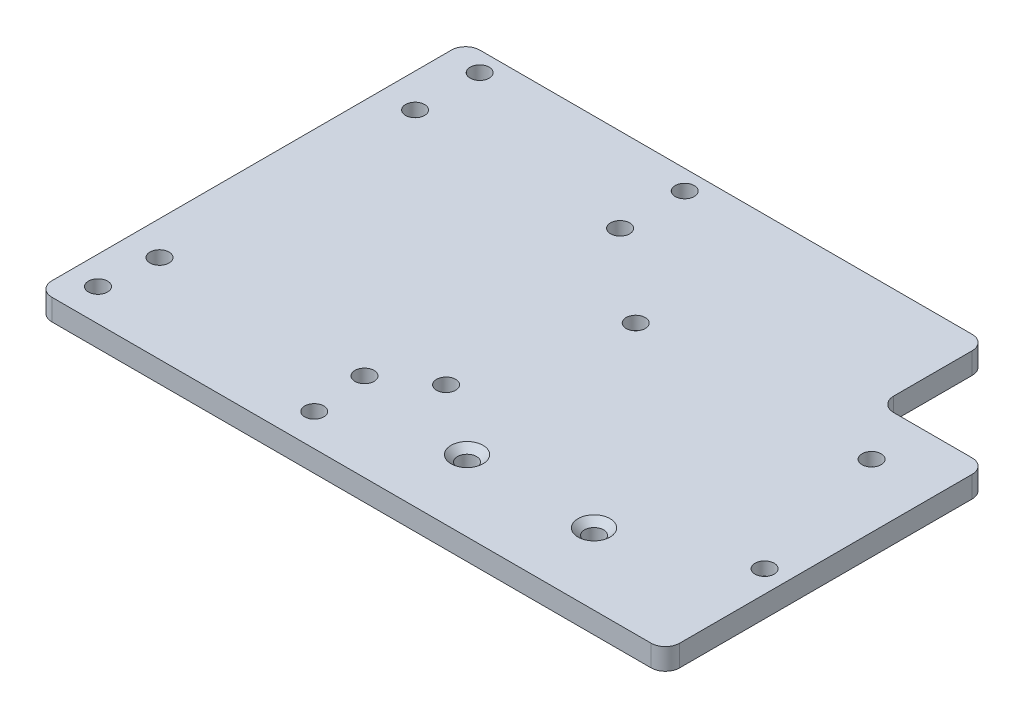
SolidWorks part; units mm, degrees
note: '?' marks a value the reader was unsure of.
ref_plane "Front Plane" through (0, 0, 0) normal (0, 0, 1) x (1, 0, 0)
ref_plane "Top Plane" through (0, 0, 0) normal (0, 1, 0) x (1, 0, 0)
ref_plane "Right Plane" through (0, 0, 0) normal (1, 0, 0) x (0, 0, -1)
sketch "Sketch1" plane through (0, 0, 0) normal (0, 1, 0) x (1, 0, 0)
  line L1 (-55.88, -38.1) -> (55.88, -38.1)
  line L2 (-55.88, -38.1) -> (-55.88, 38.1)
  line L3 (-55.88, 38.1) -> (55.88, 38.1)
  line L4 (55.88, -38.1) -> (55.88, 38.1)
  line L5 (-55.88, -38.1) -> (55.88, 38.1) construction
  line L6 (-55.88, 38.1) -> (55.88, -38.1) construction
  point P0 (0, 0)
  dimension "D1" = 111.76
  dimension "D2" = 76.2
extrude "Boss-Extrude1" add sketch "Sketch1" along normal mid plane 3.81
fillet "Fillet1" radius 2.54 4 edges at (55.88, 0, 38.1) (55.88, 0, -38.1) (-55.88, 0, -38.1) (-55.88, 0, 38.1)
hole_wizard "CSK for M3 Flat Head Machine Screw3" [suppressed] positions "Sketch2" profile "Sketch3" countersink size "M3" standard "ANSI Metric"
sketch "Sketch2" plane through (0, 1.5875, 0) normal (0, 1, 0) x (1, 0, 0)
  line L0 (-50, 24.9999) -> (50, 24.9999) construction
  line L1 (50, 24.9999) -> (50, -24.9999) construction
  line L2 (50, -24.9999) -> (-50, -24.9999) construction
  line L3 (-50, -24.9999) -> (-50, 24.9999) construction
  line L6 (0, -1.7463) -> (0, 1.7463) construction
  line L7 (-1.7463, 0) -> (1.7463, 0) construction
  point P0 (-50, 24.9999)
  point P2 (50, 24.9999)
  point P4 (50, -24.9999)
  point P6 (-50, -24.9999)
  point P20 (0, 24.9999)
  point P23 (-50, 0)
  dimension "D1" = 100
  dimension "D2" = 49.9999
sketch "Sketch3" plane through (-50, 1.5875, -24.9999) normal (1, 0, 0) x (0, 0, 1)
  line L0 (0, 0) -> (0, 3.175)
  line L1 (0, 3.175) -> (1.8, 3.175)
  line L2 (1.8, 3.175) -> (1.8, 1.35)
  line L3 (1.8, 1.35) -> (3.15, 0)
  line L5 (3.15, 0) -> (0, 0)
  line L6 (-1.8, 1.35) -> (-3.15, 0) construction
  line L11 (0, -6.35) -> (0, 107.95) construction
  dimension "Thru Hole Dia." = 3.6
  dimension "Thru Hole Depth" = 3.175
  dimension "Near C'Sink Dia." = 6.3
  dimension "Near C'Sink Angle" = 90
hole_wizard "Ø3.8 (3.8) Diameter Hole1" [suppressed] positions "Sketch4" profile "Sketch5" hole size "Ø3.8" standard "ANSI Metric"
sketch "Sketch4" plane through (0, 1.5875, 0) normal (0, 1, 0) x (1, 0, 0)
  line L0 (-1.7463, 0) -> (1.7463, 0) construction
  line L1 (-62.25, 0) -> (62.25, 0) construction
  point P0 (-62.25, 0)
  point P2 (62.25, 0)
  point P11 (0, 0)
  dimension "D1" = 124.5
sketch "Sketch5" plane through (-62.25, 1.5875, 0) normal (1, 0, 0) x (0, 0, 1)
  line L0 (0, 0) -> (0, 3.175)
  line L1 (0, 3.175) -> (1.9, 3.175)
  line L2 (1.9, 3.175) -> (1.9, 0)
  line L5 (1.9, 0) -> (0, 0)
  line L11 (0, -6.35) -> (0, 107.95) construction
  dimension "Thru Hole Dia." = 3.8
  dimension "Thru Hole Depth" = 3.175
hole_wizard "M3 Clearance Hole4" positions "Sketch6" profile "Sketch7" hole size "M3" standard "ANSI Metric" end condition through all
sketch "Sketch6" plane through (0, -1.905, 0) normal (0, -1, 0) x (-1, 0, 0)
  line L0 (13.38, 34.6) -> (49.88, 34.6) construction
  line L2 (50.88, -32.35) -> (12.38, -32.35) construction
  line L11 (53.34, -38.1) -> (-53.34, -38.1) construction
  line L13 (31.63, 34.6) -> (31.63, -32.35) construction
  line L14 (55.88, 35.56) -> (55.88, -35.56) construction
  line L15 (-53.34, 38.1) -> (53.34, 38.1) construction
  point P0 (13.38, 34.6)
  point P2 (49.88, 34.6)
  point P4 (50.88, -32.35)
  point P6 (12.38, -32.35)
  dimension "D1" = 36.5
  dimension "D2" = 5.75
  dimension "D3" = 38.5
  dimension "D4" = 3.5
  dimension "D5" = 24.25
sketch "Sketch7" plane through (-13.38, -1.905, -34.6) normal (1, 0, 0) x (0, 0, -1)
  line L0 (0, 0) -> (0, 3.81)
  line L1 (0, 3.81) -> (1.7, 3.81)
  line L2 (1.7, 3.81) -> (1.7, 0)
  line L5 (1.7, 0) -> (0, 0)
  line L11 (0, -6.35) -> (0, 107.95) construction
  dimension "Thru Hole Dia." = 3.4
  dimension "Thru Hole Depth" = 3.81
hole_wizard "CSK for M3 Flat Head Machine Screw1" positions "Sketch8" profile "Sketch9" countersink size "M3" standard "ANSI Metric" end condition up to next
sketch "Sketch8" plane through (0, -1.905, 0) normal (0, -1, 0) x (-1, 0, 0)
  line L0 (-51.9557, -16.51) -> (4.7447, -16.51) construction
  line L2 (-55.88, -35.56) -> (-55.88, 35.56) construction
  line L3 (53.34, -38.1) -> (-53.34, -38.1) construction
  line L4 (-2.6053, 9.89) -> (-44.6057, 9.89) construction
  line L7 (-23.6055, 9.89) -> (-23.6055, -16.51) construction
  point P0 (-51.9557, -16.51)
  point P2 (4.7447, -16.51)
  point P13 (-44.6057, 9.89)
  point P15 (-2.6053, 9.89)
  dimension "D1" = 56.7004
  dimension "D2" = 3.9243
  dimension "D3" = 21.59
  dimension "D4" = 7.35
  dimension "D5" = 26.4
sketch "Sketch9" plane through (51.9557, -1.905, 16.51) normal (1, 0, 0) x (0, 0, -1)
  line L0 (0, 0) -> (0, 3.81)
  line L1 (0, 3.81) -> (1.7, 3.81)
  line L2 (1.7, 3.81) -> (1.7, 1.45)
  line L3 (1.7, 1.45) -> (3.15, 0)
  line L5 (3.15, 0) -> (0, 0)
  line L6 (-1.7, 1.45) -> (-3.15, 0) construction
  line L11 (0, -6.35) -> (0, 107.95) construction
  dimension "Thru Hole Dia." = 3.4
  dimension "Thru Hole Depth" = 3.81
  dimension "Near C'Sink Dia." = 6.3
  dimension "Near C'Sink Angle" = 90
hole_wizard "CSK for M3 Flat Head Machine Screw2" positions "Sketch10" profile "Sketch11" countersink size "M3" standard "ANSI Metric" end condition up to next
sketch "Sketch10" plane through (0, -1.905, 0) normal (0, -1, 0) x (-1, 0, 0)
  line L0 (49.88, 23.1) -> (49.88, -22.4) construction
  line L4 (49.88, 23.1) -> (13.38, 23.1) construction
  line L5 (13.38, 23.1) -> (13.38, -22.4) construction
  line L6 (13.38, -22.4) -> (49.88, -22.4) construction
  line L8 (49.88, 23.1) -> (49.88, 34.6) construction
  circle A0 centre (49.88, 34.6) radius 1.7 construction
  point P0 (49.88, 23.1)
  point P2 (49.88, -22.4)
  point P17 (13.38, 23.1)
  point P19 (13.38, -22.4)
  dimension "D2" = 57
  dimension "D1" = 45.5
  dimension "D3" = 36.5
sketch "Sketch11" plane through (-49.88, -1.905, -23.1) normal (1, 0, 0) x (0, 0, -1)
  line L0 (0, 0) -> (0, 3.81)
  line L1 (0, 3.81) -> (1.7, 3.81)
  line L2 (1.7, 3.81) -> (1.7, 1.45)
  line L3 (1.7, 1.45) -> (3.15, 0)
  line L5 (3.15, 0) -> (0, 0)
  line L6 (-1.7, 1.45) -> (-3.15, 0) construction
  line L11 (0, -6.35) -> (0, 107.95) construction
  dimension "Thru Hole Dia." = 3.4
  dimension "Thru Hole Depth" = 3.81
  dimension "Near C'Sink Dia." = 6.3
  dimension "Near C'Sink Angle" = 90
sketch "Sketch23" plane through (0, -1.905, 0) normal (0, -1, 0) x (1, 0, 0)
  circle A0 centre (-13.38, 22.4) radius 3.15 construction
  circle A1 centre (-49.88, 22.4) radius 3.15 construction
  circle A2 centre (-13.38, 22.4) radius 3.15
  circle A3 centre (-49.88, 22.4) radius 3.15
  circle A4 centre (-13.38, 22.4) radius 1.7 construction
  circle A5 centre (-49.88, 22.4) radius 1.7 construction
  circle A6 centre (-13.38, 22.4) radius 1.7
  circle A7 centre (-49.88, 22.4) radius 1.7
extrude "Boss-Extrude2" add sketch "Sketch23" against normal up to surface (3.81 mm away) up to face at (-49.88, 1.905, -24.8)
sketch "Sketch12" plane through (0, -1.905, 0) normal (0, -1, 0) x (1, 0, 0)
  line L1 (65.1855, -44.4378) -> (36.83, -44.4378)
  line L2 (65.1855, -44.4378) -> (65.1855, -19.05)
  line L3 (65.1855, -19.05) -> (36.83, -19.05)
  line L4 (36.83, -44.4378) -> (36.83, -19.05)
  line L5 (55.88, 35.56) -> (55.88, -35.56) construction
  line L7 (53.34, -38.1) -> (-53.34, -38.1) construction
  dimension "D1" = 19.05
  dimension "D2" = 19.05
extrude "Cut-Extrude1" cut sketch "Sketch12" against normal through all
hole_wizard "M3 Clearance Hole1" positions "Sketch15" profile "Sketch16" hole size "M3" standard "ANSI Metric" end condition up to next
sketch "Sketch15" plane through (0, -1.905, 0) normal (0, -1, 0) x (-1, 0, 0)
  line L0 (-30.48, -25.4) -> (-7.874, -25.4) construction
  line L2 (53.34, -38.1) -> (-53.34, -38.1) construction
  line L3 (-55.88, -35.56) -> (-55.88, 19.05) construction
  point P0 (-30.48, -25.4)
  point P2 (-7.874, -25.4)
  dimension "D1" = 22.606
  dimension "D2" = 12.7
  dimension "D3" = 25.4
sketch "Sketch16" plane through (30.48, -1.905, 25.4) normal (1, 0, 0) x (0, 0, -1)
  line L0 (0, 0) -> (0, 3.81)
  line L1 (0, 3.81) -> (2.85, 3.81)
  line L2 (1.7, 2.66) -> (1.7, 0)
  line L5 (1.7, 0) -> (0, 0)
  line L7 (2.85, 3.81) -> (1.7, 2.66)
  line L8 (-2.85, 3.81) -> (-1.7, 2.66) construction
  line L11 (0, -6.35) -> (0, 107.95) construction
  dimension "Thru Hole Dia." = 3.4
  dimension "Thru Hole Depth" = 3.81
  dimension "Far C'Sink Dia." = 5.7
  dimension "Far C'Sink Angle" = 90
fillet "Fillet2" radius 2.54 3 edges at (55.88, 0, -19.05) (36.83, 0, -19.05) (36.83, 0, -38.1)
ref_axis "Axis1" [suppressed] through (-50, -1.5875, 24.9999) along (0, 1, 0)?
ref_axis "Axis2" [suppressed] through (50, -1.5875, 24.9999) along (0, 1, 0)?
sketch "Sketch17" [suppressed] plane through (0, 1.905, 0) normal (0, 1, 0) x (1, 0, 0)
  line L0 (-9.88, 0) -> (-55.88, 0) construction
  line L1 (-9.88, 50.8) -> (79.6695, 50.8)
  line L2 (-9.88, 50.8) -> (-9.88, -50.8)
  line L3 (-9.88, -50.8) -> (79.6695, -50.8)
  line L4 (79.6695, 50.8) -> (79.6695, -50.8)
  line L5 (-55.88, 34.925) -> (-55.88, -34.925) construction
  dimension "D1" = 101.6
  dimension "D2" = 46
extrude "Cut-Extrude2" [suppressed] cut sketch "Sketch17" against normal through all both and the other way through all
sketch "Sketch18" [suppressed] plane through (0, 1.905, 0) normal (0, 1, 0) x (1, 0, 0)
  line L0 (-52.705, -38.1) -> (-9.88, -38.1) construction
  line L1 (-37.43, -25.4) -> (-18.38, -25.4)
  line L2 (-37.43, -25.4) -> (-37.43, -44.45)
  line L3 (-37.43, -44.45) -> (-18.38, -44.45)
  line L4 (-18.38, -25.4) -> (-18.38, -44.45)
  line L6 (-9.88, -38.1) -> (-9.88, 38.1) construction
  circle A0 centre (-14.63, -32.35) radius 3.6 construction
  dimension "D5" = 7.2
  dimension "D1" = 19.05
  dimension "D2" = 8.5
  dimension "D3" = 19.05
  dimension "D4" = 12.7
extrude "Cut-Extrude3" [suppressed] cut sketch "Sketch18" against normal through all
fillet "Fillet3" [suppressed] radius 3.175
hole_wizard "M3 Clearance Hole3" [suppressed] positions "Sketch19" profile "Sketch20" hole size "M3" standard "ANSI Metric"
sketch "Sketch19" plane through (0, 1.905, 0) normal (0, 1, 0) x (1, 0, 0)
  line L0 (-52.13, 34.6) -> (-52.13, 7.1) construction
  line L1 (-52.13, 7.1) -> (-13.63, 7.1) construction
  point P0 (-52.13, 7.1)
  point P2 (-13.63, 7.1)
  dimension "D1" = 27.5
  dimension "D2" = 38.5
sketch "Sketch20" plane through (-52.13, 1.905, -7.1) normal (1, 0, 0) x (0, 0, 1)
  line L0 (0, 0) -> (0, 3.81)
  line L1 (0, 3.81) -> (1.8, 3.81)
  line L2 (1.8, 3.81) -> (1.8, 0)
  line L5 (1.8, 0) -> (0, 0)
  line L11 (0, -6.35) -> (0, 107.95) construction
  dimension "Thru Hole Dia." = 3.6
  dimension "Thru Hole Depth" = 3.81
sketch "Sketch21" [suppressed] plane through (0, -1.905, 0) normal (0, -1, 0) x (1, 0, 0)
  line L0 (-51.13, 32.35) -> (-14.63, 32.35) construction
  line L1 (-13.055, -38.1) -> (-52.705, -38.1) construction
  point P4 (-32.88, 32.35)
  point P7 (-32.88, -38.1)
  dimension "D1" = 0
